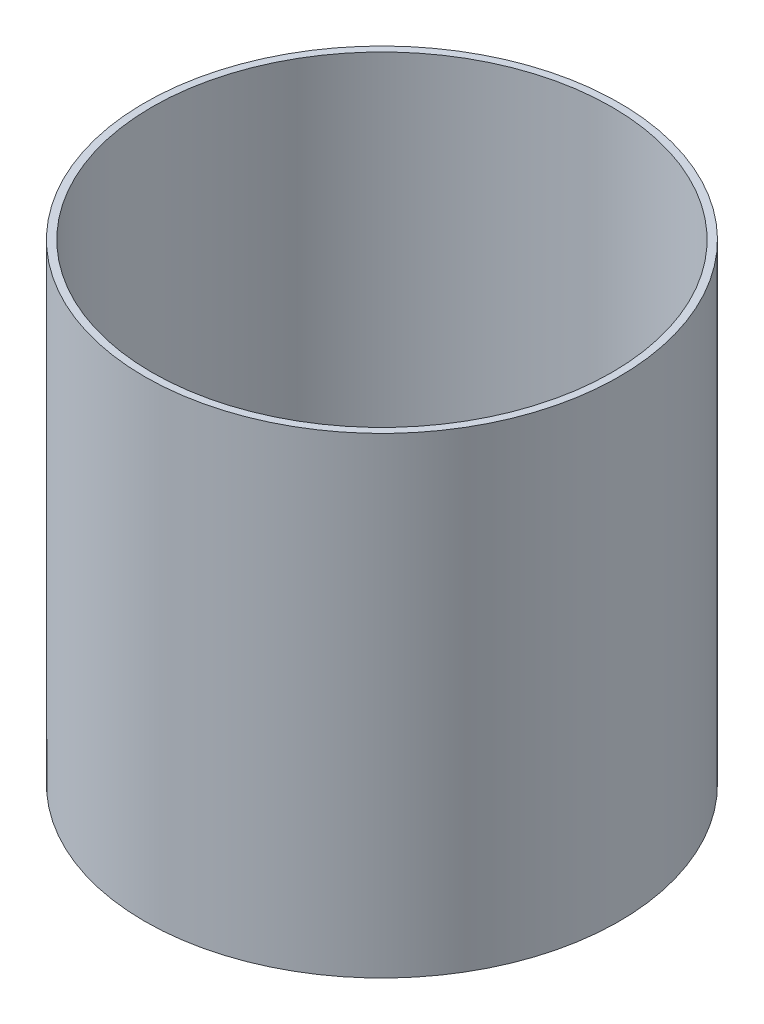
SolidWorks part; units mm, degrees
ref_plane "Front Plane" through (0, 0, 0) normal (0, 0, 1) x (1, 0, 0)
ref_plane "Top Plane" through (0, 0, 0) normal (0, 1, 0) x (1, 0, 0)
ref_plane "Right Plane" through (0, 0, 0) normal (1, 0, 0) x (0, 0, -1)
sketch "Sketch1" plane through (0, 0, 0) normal (0, 1, 0) x (1, 0, 0)
  circle A0 centre (0, 0) radius 51.1048
  circle A1 centre (0, 0) radius 49.53
  dimension "D1" = 102.2096
  dimension "D2" = 99.06
extrude "Boss-Extrude1" add sketch "Sketch1" along normal blind 101.6
equation "\"Body_Tube_OD\"= 4.024in"
equation "\"Body_Tube_ID\"= 3.90in"
equation "\"D1@Sketch1\"=\"Body_Tube_OD\""
equation "\"D2@Sketch1\"=\"Body_Tube_ID\""
equation "\"Mid_Section_Length\" = 4in"
equation "\"D1@Boss-Extrude1\"=\"Mid_Section_Length\""
